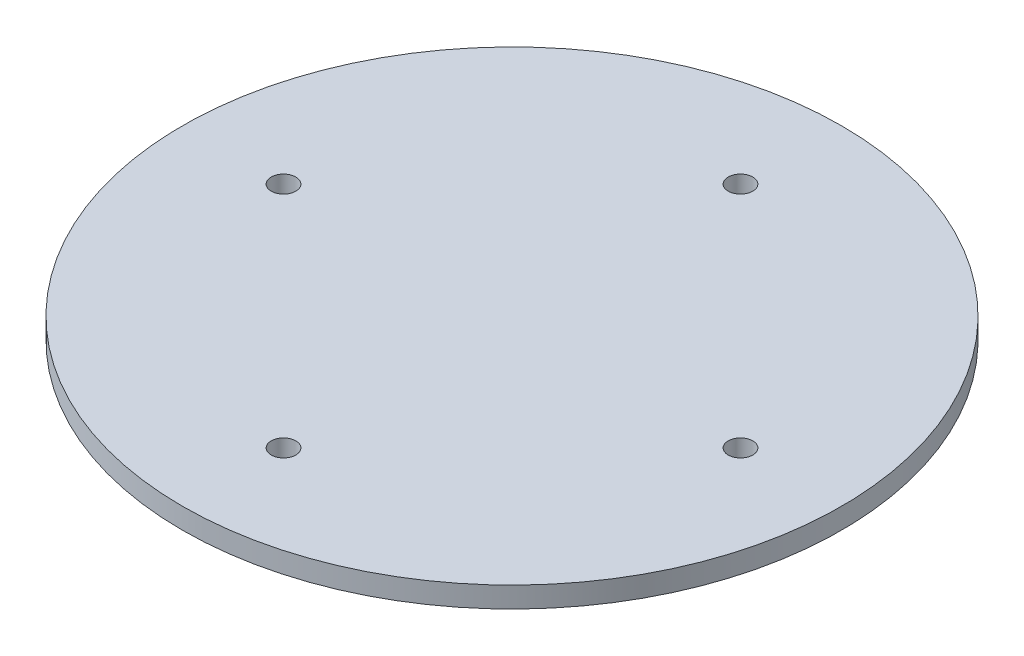
SolidWorks part; units mm, degrees
ref_plane "Front Plane" through (0, 0, 0) normal (0, 0, 1) x (1, 0, 0)
ref_plane "Top Plane" through (0, 0, 0) normal (0, 1, 0) x (1, 0, 0)
ref_plane "Right Plane" through (0, 0, 0) normal (1, 0, 0) x (0, 0, -1)
sketch "Sketch1" plane through (0, 0, 0) normal (0, 1, 0) x (1, 0, 0)
  circle A0 centre (0, 0) radius 47.625
  dimension "D1" = 95.25
extrude "Boss-Extrude1" add sketch "Sketch1" along normal blind 3
sketch "Sketch3" plane through (0, 3, 0) normal (0, 1, 0) x (1, 0, 0)
  line L0 (0, 0) -> (33.02, 0) construction
  circle A0 centre (33.02, 0) radius 1.778
  dimension "D1" = 3.556
  dimension "D2" = 33.02
extrude "Cut-Extrude1" cut sketch "Sketch3" against normal through all
pattern_circular "CirPattern1" count 4 over 360 about axis through (0, 3, 0) along (0, -1, 0) of "Cut-Extrude1"
sketch "Sketch4" plane through (0, 3, 0) normal (0, 1, 0) x (1, 0, 0)
  line L0 (-2.5981, 1.5) -> (2.5981, 1.5)
  arc A0 (-2.5981, 1.5) -> (2.5981, 1.5) centre (0, 0) ccw
  dimension "D1" = 6
  dimension "D2" = 1.5
extrude "Cut-Extrude2" [suppressed] cut sketch "Sketch4" against normal through all
